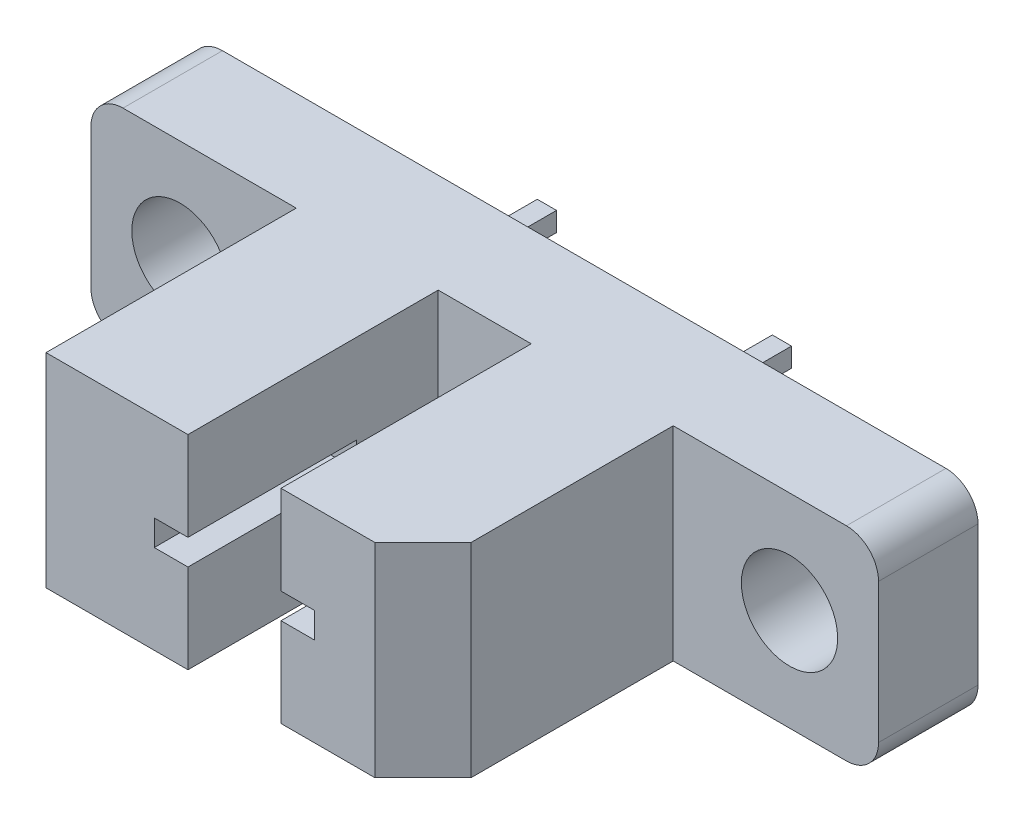
SolidWorks part; units mm, degrees
ref_plane "Plano frontal" through (0, 0, 0) normal (0, 0, 1) x (1, 0, 0)
ref_plane "Plano superior" through (0, 0, 0) normal (0, 1, 0) x (1, 0, 0)
ref_plane "Plano direito" through (0, 0, 0) normal (1, 0, 0) x (0, 0, -1)
sketch "Esboço1" plane through (0, 0, 0) normal (0, 0, 1) x (1, 0, 0)
  line L0 (-9.5, 0) -> (9.5, 0) construction
  line L1 (-12.275, 3.175) -> (12.275, 3.175)
  line L2 (-12.275, 3.175) -> (-12.275, -3.175)
  line L3 (-12.275, -3.175) -> (12.275, -3.175)
  line L4 (12.275, 3.175) -> (12.275, -3.175)
  line L5 (-12.275, 3.175) -> (12.275, -3.175) construction
  line L6 (-12.275, -3.175) -> (12.275, 3.175) construction
  circle A0 centre (-9.5, 0) radius 1.5
  circle A1 centre (9.5, 0) radius 1.5
  point P0 (0, 0)
  point P9 (0, 0)
  dimension "D4" = 3
  dimension "D1" = 24.55
  dimension "D2" = 6.35
  dimension "D3" = 19
extrude "Ressalto-extrusão1" add sketch "Esboço1" along normal blind 3.1
sketch "Esboço2" plane through (0, 0, 3.1) normal (0, 0, 1) x (1, 0, 0)
  line L0 (12.275, 3.175) -> (-12.275, 3.175) construction
  line L1 (-5.875, 3.175) -> (5.875, 3.175)
  line L2 (-5.875, 3.175) -> (-5.875, -3.175)
  line L3 (-5.875, -3.175) -> (5.875, -3.175)
  line L4 (5.875, 3.175) -> (5.875, -3.175)
  line L5 (-12.275, -3.175) -> (12.275, -3.175) construction
  line L6 (0, -3.175) -> (0, 3.175) construction
  point P11 (0, 3.175)
  dimension "D1" = 11.75
extrude "Ressalto-extrusão2" add sketch "Esboço2" along normal blind 7.8
sketch "Esboço5" plane through (0, 0, 10.9) normal (0, 0, 1) x (1, 0, 0)
  line L0 (-5.875, 0) -> (5.875, 0) construction
  line L1 (-5.875, 3.175) -> (-5.875, -3.175) construction
  line L2 (5.875, -3.175) -> (5.875, 3.175) construction
  line L3 (0, 3.175) -> (0, -3.175) construction
  line L4 (5.875, 3.175) -> (-5.875, 3.175) construction
  line L5 (-5.875, -3.175) -> (5.875, -3.175) construction
  line L7 (-2.5, 0.4) -> (2.5, 0.4)
  line L8 (-2.5, 0.4) -> (-2.5, -0.4)
  line L9 (-2.5, -0.4) -> (2.5, -0.4)
  line L10 (2.5, 0.4) -> (2.5, -0.4)
  point P16 (0, 0.4)
  point P17 (-2.5, 0)
  dimension "D1" = 0.8
  dimension "D2" = 5
extrude "Corte-extrusão2" cut sketch "Esboço5" against normal blind 5.25
sketch "Esboço3" plane through (0, 0, 10.9) normal (0, 0, 1) x (1, 0, 0)
  line L0 (0, 3.175) -> (0, -3.175) construction
  line L1 (5.875, 3.175) -> (-5.875, 3.175) construction
  line L2 (-5.875, -3.175) -> (5.875, -3.175) construction
  line L4 (-1.45, 3.175) -> (1.45, 3.175)
  line L5 (-1.45, 3.175) -> (-1.45, -3.175)
  line L6 (-1.45, -3.175) -> (1.45, -3.175)
  line L7 (1.45, 3.175) -> (1.45, -3.175)
  point P10 (0, 3.175)
  dimension "D1" = 2.9
extrude "Corte-extrusão1" cut sketch "Esboço3" against normal up to surface (7.8 mm away) up to face at (-9.075, 0, 3.1)
chamfer "Chanfro3" distance 1.5 angle 45 1 edges at (5.875, 0, 10.9)
fillet "Filete1" radius 1 4 edges at (12.275, -3.175, 1.55) (12.275, 3.175, 1.55) (-12.275, 3.175, 1.55) (-12.275, -3.175, 1.55)
ref_plane "Plano1" through (0, 0, 4.1) normal (0, 0, 1) x (1, 0, 0)
sketch "Esboço8" plane through (0, 0, 4.1) normal (0, 0, 1) x (1, 0, 0)
  line L0 (1.45, 3.175) -> (1.45, -3.175)
  line L1 (-1.45, -3.175) -> (-1.45, 3.175)
  line L2 (5.875, -3.175) -> (5.875, 3.175)
  line L3 (-5.875, 3.175) -> (-5.875, -3.175)
  line L4 (-5.875, -3.175) -> (-1.45, -3.175)
  line L5 (1.45, -3.175) -> (5.875, -3.175)
  line L6 (5.875, 3.175) -> (1.45, 3.175)
  line L7 (-1.45, 3.175) -> (-5.875, 3.175)
  line L8 (-1.45, 3.175) -> (-5.875, 3.175)
  line L9 (5.875, 3.175) -> (1.45, 3.175)
  line L10 (1.45, -3.175) -> (5.875, -3.175)
  line L11 (-5.875, -3.175) -> (-1.45, -3.175)
  line L12 (-5.875, 3.175) -> (-5.875, -3.175)
  line L13 (5.875, -3.175) -> (5.875, 3.175)
  line L14 (-1.45, -3.175) -> (-1.45, 3.175)
  line L15 (1.45, 3.175) -> (1.45, -3.175)
sketch "Esboço9" plane through (0, 0, 0) normal (0, 0, -1) x (-1, 0, 0)
  line L0 (-3.6625, 3.175) -> (-3.6625, -3.175) construction
  line L1 (3.6625, 3.175) -> (3.6625, -3.175) construction
  line L2 (-5.875, 0) -> (-1.45, 0) construction
  line L3 (1.45, 0) -> (5.875, 0) construction
  line L4 (-1.45, 3.175) -> (-5.875, 3.175)
  line L5 (-1.45, -3.175) -> (-1.45, 3.175)
  line L6 (-5.875, -3.175) -> (-1.45, -3.175)
  line L7 (-5.875, 3.175) -> (-5.875, -3.175)
  line L8 (-1.45, 3.175) -> (-5.875, 3.175)
  line L9 (-1.45, -3.175) -> (-1.45, 3.175)
  line L10 (-5.875, -3.175) -> (-1.45, -3.175)
  line L11 (-5.875, 3.175) -> (-5.875, -3.175)
  line L12 (5.875, 3.175) -> (1.45, 3.175)
  line L13 (5.875, -3.175) -> (5.875, 3.175)
  line L14 (1.45, -3.175) -> (5.875, -3.175)
  line L15 (1.45, 3.175) -> (1.45, -3.175)
  line L16 (5.875, 3.175) -> (1.45, 3.175)
  line L17 (5.875, -3.175) -> (5.875, 3.175)
  line L18 (1.45, -3.175) -> (5.875, -3.175)
  line L19 (1.45, 3.175) -> (1.45, -3.175)
  line L20 (-3.9625, 1.27) -> (-3.3625, 1.27) construction
  line L21 (-3.9625, 1.57) -> (-3.3625, 1.57)
  line L22 (-3.9625, 1.57) -> (-3.9625, 0.97)
  line L23 (-3.9625, 0.97) -> (-3.3625, 0.97)
  line L24 (-3.3625, 1.57) -> (-3.3625, 0.97)
  line L25 (-3.6625, 1.57) -> (-3.6625, 0.97) construction
  dimension "D3" = 0.6
  dimension "D4" = 1.27
  dimension "D1" = 0
  dimension "D2" = 0
extrude "Ressalto-extrusão3" add sketch "Esboço9" along normal blind 2.5 contours L22 L21 L24 L23
ref_plane "Plano2" through (0, 0, 0) normal (0, 1, 0) x (1, 0, 0)
ref_plane "Plano3" through (0, 0, 0) normal (-1, 0, 0) x (0, 0, 1)
mirror "Espelhar1" about plane through (0, 0, 0) normal (0, 1, 0) of "Ressalto-extrusão3"
mirror "Espelhar2" about plane through (0, 0, 0) normal (-1, 0, 0) of "Espelhar1", "Ressalto-extrusão3"
ref_axis "Eixo1" through (9.5, 0, 3.1) along (0, 0, -1)
ref_plane "Plano5" through (0, 0, 3.1) normal (0, 0, 1) x (1, 0, 0)
ref_plane "Plano6" through (0, 0, 0) normal (0, 0, -1) x (-1, 0, 0)
